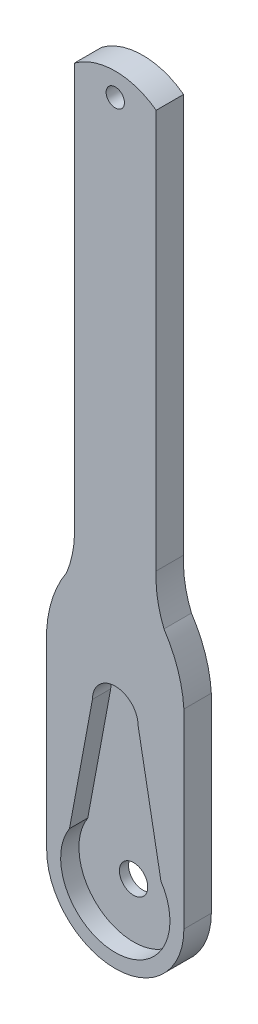
SolidWorks part; units mm, degrees
ref_plane "Front Plane" through (0, 0, 0) normal (0, 0, 1) x (1, 0, 0)
ref_plane "Top Plane" through (0, 0, 0) normal (0, 1, 0) x (1, 0, 0)
ref_plane "Right Plane" through (0, 0, 0) normal (1, 0, 0) x (0, 0, -1)
sketch "Sketch1" plane through (0, 0, 0) normal (0, 0, 1) x (1, 0, 0)
  line L0 (5, 24.25) -> (2.4925, 10.7598)
  line L1 (0, 0) -> (15, 0)
  line L2 (0, 0) -> (0, 85)
  line L3 (0, 85) -> (15, 85)
  line L4 (15, 0) -> (15, 85)
  line L5 (7.5, 0) -> (15, 0)
  line L6 (15, 0) -> (15, 7.5)
  line L7 (7.5, 7.5) -> (7.5, 26.75) construction
  line L10 (10, 24.25) -> (12.4925, 10.7826)
  arc A0 (0, 7.5) -> (15, 7.5) centre (7.5, 7.5) ccw
  arc A2 (10, 24.25) -> (5, 24.25) centre (7.5, 24.25) ccw
  arc A3 (2.4925, 10.7598) -> (12.4925, 10.7826) centre (7.5, 7.5) ccw
  point P17 (2.4925, 10.7826)
  dimension "D3" = 10
  dimension "D4" = 5.975
  dimension "D6" = 5
  dimension "D1" = 15
  dimension "D2" = 85
  dimension "D5" = 19.25
extrude "Boss-Extrude1" add sketch "Sketch1" along normal blind 3 contours L2 A0 L4 L3 A2 region at (7.5003, 49.2811, 0)
extrude "Boss-Extrude2" add sketch "Sketch1<3>" along normal blind 1 contours A2 region at (7.4985, 12.5376, 0)
sketch "Sketch1<3>" plane through (0, 0, 0) normal (0, 0, 1) x (1, 0, 0) same geometry as "Sketch1"
sketch "Sketch2" plane through (0, 0, 3) normal (0, 0, 1) x (1, 0, 0)
  line L0 (0, 85) -> (15, 85) construction
  line L1 (15, 7.5) -> (15, 85) construction
  line L3 (0, 85) -> (7.5, 85)
  line L4 (7.5, 85) -> (8.366, 85)
  line L6 (0, 7.5) -> (0, 85) construction
  line L7 (7.5, 91.1947) -> (7.5, -46.3008) construction
  line L8 (3.0299, 39.8913) -> (3.0299, 83.5223)
  line L9 (11.9701, 39.8913) -> (11.9701, 83.5223)
  arc A0 (11.9701, 83.5223) -> (3.0299, 83.5223) centre (7.5, 77.5) ccw
  arc A2 (10, 24.25) -> (5, 24.25) centre (7.5, 24.25) ccw construction
  arc A3 (0, 26.75) -> (2.1738, 34.8326) centre (13.1666, 27.5424) cw
  arc A4 (2.1738, 34.8326) -> (3.0299, 39.8913) centre (-8.6706, 39.2695) ccw
  arc A5 (12.8262, 34.8326) -> (11.9701, 39.8913) centre (23.6706, 39.2695) cw
  arc A6 (15, 26.75) -> (12.8262, 34.8326) centre (1.8334, 27.5424) ccw
  circle A9 centre (7.5, 82.5) radius 1
  arc A10 (2.4925, 10.7598) -> (12.4925, 10.7826) centre (7.5, 7.5) ccw construction
  circle A11 centre (7.5, 7.5) radius 1.55
  point P8 (7.5, 26.75)
  line M7 (0, 85) -> (0, 7.5)
  line M9 (15, 7.5) -> (15, 85)
  line M10 (15, 85) -> (0, 85)
  dimension "D1" = 2
  dimension "D3" = 3.1
  dimension "D2" = 75
extrude "Cut-Extrude1" cut sketch "Sketch2" against normal through all contours A0 M10 M7 | A0 M9 M10 | A9 | A11 region at (13.4872, 59.5795, 3) region at (1.5128, 59.5795, 3)
